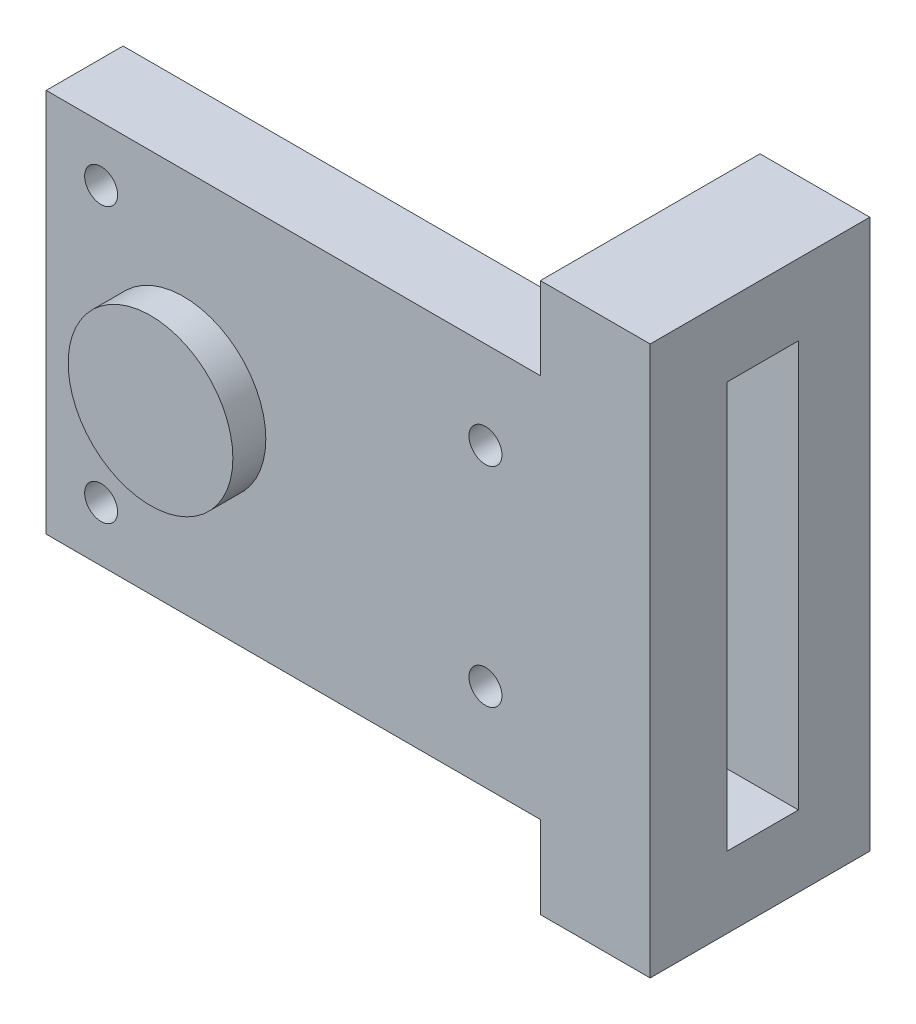
SolidWorks part; units mm, degrees
ref_plane "Front Plane" through (0, 0, 0) normal (0, 0, 1) x (1, 0, 0)
ref_plane "Top Plane" through (0, 0, 0) normal (0, 1, 0) x (1, 0, 0)
ref_plane "Right Plane" through (0, 0, 0) normal (1, 0, 0) x (0, 0, -1)
sketch "Sketch1" plane through (0, 0, 0) normal (0, 0, 1) x (1, 0, 0)
  line L1 (-92.5, 17.5) -> (-47.5, 17.5)
  line L2 (-92.5, 17.5) -> (-92.5, -17.5)
  line L3 (-92.5, -17.5) -> (-47.5, -17.5)
  line L4 (-47.5, 17.5) -> (-47.5, -17.5)
  line L5 (-92.5, 0) -> (-56.7435, 0) construction
  circle A0 centre (-87.5, 12.5) radius 1.5
  circle A1 centre (-87.5, -12.5) radius 1.5
  circle A2 centre (-52.5, 9.5) radius 1.5
  circle A3 centre (-52.5, -9.5) radius 1.5
  circle A4 centre (-80, 0) radius 4.25
  dimension "D2" = 3
  dimension "D5" = 8.5
  dimension "D1" = 45
  dimension "D3" = 5
  dimension "D4" = 5
extrude "Boss-Extrude1" add sketch "Sketch1" along normal blind 7 contours L4 L1 L2 A4 L3 A3 A2 A0 A1 | L5 A4 | A4 L5 region at (-80, 1.8038, 0) region at (-80, -1.8038, 0) region at (-70, 16.9299, 0)
sketch "Sketch2" plane through (-47.5, 0, 0) normal (1, 0, 0) x (0, 0, -1)
  line L1 (0, 25) -> (-7, 25)
  line L2 (0, 25) -> (0, -25)
  line L3 (0, -25) -> (-7, -25)
  line L4 (-7, 25) -> (-7, -25)
  line L6 (-7, 17.5) -> (0, 17.5) construction
  line L7 (-7, -17.5) -> (0, -17.5) construction
  line L8 (-7, 17.5) -> (-7, -17.5) construction
  dimension "D2" = 7.5
  dimension "D3" = 7.5
extrude "Boss-Extrude2" add sketch "Sketch2" along normal blind 10
sketch "Sketch3" plane through (0, 0, 0) normal (0, 0, -1) x (-1, 0, 0)
  line L0 (37.5, -25) -> (37.5, 25) construction
  line L1 (47.5, 25) -> (37.5, 25)
  line L2 (47.5, 25) -> (47.5, 18.5)
  line L3 (47.5, 18.5) -> (37.5, 18.5)
  line L4 (37.5, 25) -> (37.5, 18.5)
  line L5 (92.5, 17.5) -> (47.5, 17.5) construction
  line L6 (13.2, 0) -> (-13.2, 0) construction
  line L7 (47.5, -18.5) -> (37.5, -18.5)
  line L8 (37.5, -25) -> (37.5, -18.5)
  line L9 (47.5, -25) -> (37.5, -25)
  line L10 (47.5, -25) -> (47.5, -18.5)
  dimension "D1" = 1
extrude "Boss-Extrude3" add sketch "Sketch3" along normal blind 6.5
sketch "Sketch4" plane through (0, 0, -6.5) normal (0, 0, -1) x (-1, 0, 0)
  line L1 (47.5, 25) -> (37.5, 25)
  line L2 (47.5, 25) -> (47.5, -25)
  line L3 (47.5, -25) -> (37.5, -25)
  line L4 (37.5, 25) -> (37.5, -25)
extrude "Boss-Extrude4" add sketch "Sketch4" along normal blind 6.5
sketch "Sketch5" plane through (0, 0, 7) normal (0, 0, 1) x (1, 0, 0)
  circle A0 centre (-80, 0) radius 7.5
  dimension "D1" = 15
extrude "Boss-Extrude5" add sketch "Sketch5" along normal blind 3
extrude "Cut-Extrude1" cut sketch "Sketch1<3>" along normal blind 6 contours L5 A4 | A4 L5 region at (-80, 1.8038, 0) region at (-80, -1.8038, 0)
sketch "Sketch1<3>" plane through (0, 0, 0) normal (0, 0, 1) x (1, 0, 0) same geometry as "Sketch1"
